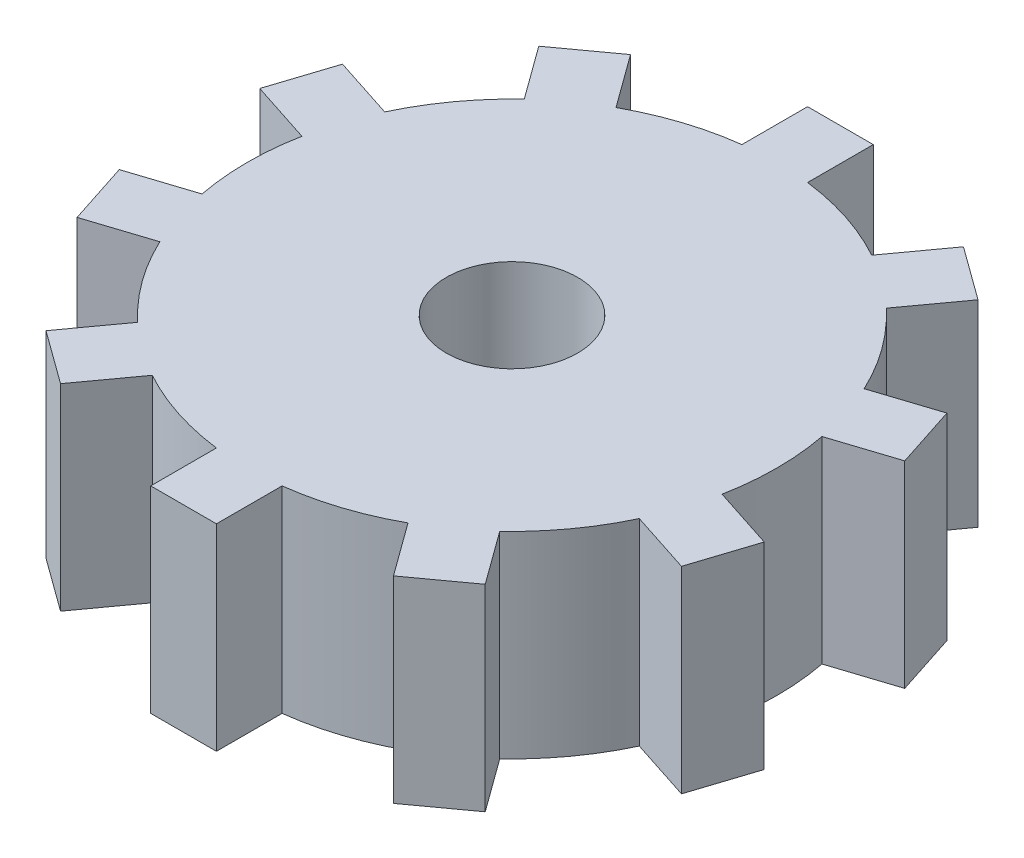
SolidWorks part; units mm, degrees
ref_plane "前基準面" through (0, 0, 0) normal (0, 0, 1) x (1, 0, 0)
ref_plane "上基準面" through (0, 0, 0) normal (0, 1, 0) x (1, 0, 0)
ref_plane "右基準面" through (0, 0, 0) normal (1, 0, 0) x (0, 0, -1)
sketch "草圖1" plane through (0, 0, 0) normal (0, 1, 0) x (1, 0, 0)
  line L0 (0, 0) -> (0, 63.9993) construction
  line L1 (33.4343, 37.5119) -> (25.3442, 43.3898)
  line L2 (5, 50) -> (-5, 50)
  line L3 (5, 50) -> (5, 40)
  line L5 (-5, 50) -> (-5, 40)
  line L6 (0, 49.7494) -> (0, 50) construction
  line L7 (5, 45) -> (-5, 45) construction
  line L8 (33.4343, 37.5119) -> (27.5565, 29.4218)
  line L10 (25.3442, 43.3898) -> (19.4663, 35.2996)
  line L11 (29.2419, 40.2481) -> (29.3893, 40.4508) construction
  line L12 (30.4954, 33.4668) -> (22.4053, 39.3447) construction
  line L13 (49.0979, 10.6956) -> (46.0077, 20.2061)
  line L14 (49.0979, 10.6956) -> (39.5873, 7.6054)
  line L16 (46.0077, 20.2061) -> (36.4972, 17.116)
  line L17 (47.3145, 15.3734) -> (47.5528, 15.4508) construction
  line L18 (44.3426, 9.1505) -> (41.2525, 18.661) construction
  line L19 (46.0077, -20.2061) -> (49.0979, -10.6956)
  line L20 (46.0077, -20.2061) -> (36.4972, -17.116)
  line L22 (49.0979, -10.6956) -> (39.5873, -7.6054)
  line L23 (47.3145, -15.3734) -> (47.5528, -15.4508) construction
  line L24 (41.2525, -18.661) -> (44.3426, -9.1505) construction
  line L25 (25.3442, -43.3898) -> (33.4343, -37.5119)
  line L26 (25.3442, -43.3898) -> (19.4663, -35.2996)
  line L28 (33.4343, -37.5119) -> (27.5565, -29.4218)
  line L29 (29.2419, -40.2481) -> (29.3893, -40.4508) construction
  line L30 (22.4053, -39.3447) -> (30.4954, -33.4668) construction
  line L31 (-5, -50) -> (5, -50)
  line L32 (-5, -50) -> (-5, -40)
  line L34 (5, -50) -> (5, -40)
  line L35 (0, -49.7494) -> (0, -50) construction
  line L36 (-5, -45) -> (5, -45) construction
  line L37 (-33.4343, -37.5119) -> (-25.3442, -43.3898)
  line L38 (-33.4343, -37.5119) -> (-27.5565, -29.4218)
  line L40 (-25.3442, -43.3898) -> (-19.4663, -35.2996)
  line L41 (-29.2419, -40.2481) -> (-29.3893, -40.4508) construction
  line L42 (-30.4954, -33.4668) -> (-22.4053, -39.3447) construction
  line L43 (-49.0979, -10.6956) -> (-46.0077, -20.2061)
  line L44 (-49.0979, -10.6956) -> (-39.5873, -7.6054)
  line L45 (-47.7477, -14.0399) -> (-47.3145, -15.3734)
  line L46 (-46.0077, -20.2061) -> (-36.4972, -17.116)
  line L47 (-47.3145, -15.3734) -> (-47.5528, -15.4508) construction
  line L48 (-44.3426, -9.1505) -> (-41.2525, -18.661) construction
  line L49 (-46.0077, 20.2061) -> (-49.0979, 10.6956)
  line L50 (-46.0077, 20.2061) -> (-36.4972, 17.116)
  line L52 (-49.0979, 10.6956) -> (-39.5873, 7.6054)
  line L53 (-47.3145, 15.3734) -> (-47.5528, 15.4508) construction
  line L54 (-41.2525, 18.661) -> (-44.3426, 9.1505) construction
  line L55 (-25.3442, 43.3898) -> (-33.4343, 37.5119)
  line L56 (-25.3442, 43.3898) -> (-19.4663, 35.2996)
  line L58 (-33.4343, 37.5119) -> (-27.5565, 29.4218)
  line L59 (-29.2419, 40.2481) -> (-29.3893, 40.4508) construction
  line L60 (-22.4053, 39.3447) -> (-30.4954, 33.4668) construction
  line L61 (-42.7975, -13.9058) -> (-66.3356, -21.5537) construction
  line L62 (-26.4503, -36.4058) -> (-40.9977, -56.4284) construction
  line L63 (0, -45) -> (0, -69.7494) construction
  line L64 (26.4503, -36.4058) -> (40.9977, -56.4284) construction
  line L65 (42.7975, -13.9058) -> (66.3356, -21.5537) construction
  line L66 (42.7975, 13.9058) -> (66.3356, 21.5537) construction
  line L67 (26.4503, 36.4058) -> (40.9977, 56.4284) construction
  arc A0 (-5, 40) -> (-19.4663, 35.2996) centre (0, 0) ccw
  circle A1 centre (0, 0) radius 10
  arc A2 (-27.5565, 29.4218) -> (-36.4972, 17.116) centre (0, 0) ccw
  arc A3 (-39.5873, 7.6054) -> (-39.5873, -7.6054) centre (0, 0) ccw
  arc A4 (-36.4972, -17.116) -> (-27.5565, -29.4218) centre (0, 0) ccw
  arc A5 (-19.4663, -35.2996) -> (-5, -40) centre (0, 0) ccw
  arc A6 (5, -40) -> (19.4663, -35.2996) centre (0, 0) ccw
  arc A7 (27.5565, -29.4218) -> (36.4972, -17.116) centre (0, 0) ccw
  arc A8 (39.5873, -7.6054) -> (39.5873, 7.6054) centre (0, 0) ccw
  arc A9 (36.4972, 17.116) -> (27.5565, 29.4218) centre (0, 0) ccw
  arc A10 (19.4663, 35.2996) -> (5, 40) centre (0, 0) ccw
  point P4 (0, 45)
  point P11 (26.4503, 36.4058)
  point P23 (42.7975, 13.9058)
  point P32 (42.7975, -13.9058)
  point P41 (26.4503, -36.4058)
  point P50 (0, -45)
  point P61 (-26.4503, -36.4058)
  point P70 (-42.7975, -13.9058)
  point P79 (-42.7975, 13.9058)
  point P88 (-26.4503, 36.4058)
  point P97 (0, 0)
  dimension "D1" = 100
  dimension "D2" = 20
  dimension "D3" = 10
  dimension "D4" = 10
  dimension "D5" = 10
extrude "填料-伸長1" add sketch "草圖1" along normal blind 30 contours L10 A10 L3 L2 L5 A0 L56 L55 L58 A2 L50 L49 L52 A3 L44 L43 L46 A4 L38 L37 L40 A5 L32 L31 L34 A6 L26 L25 L28 A7 L20 L19 L22 A8 L14 L13 L16 A9 L8 L1 A1 region at (29.3616, 0, -34.2906)
